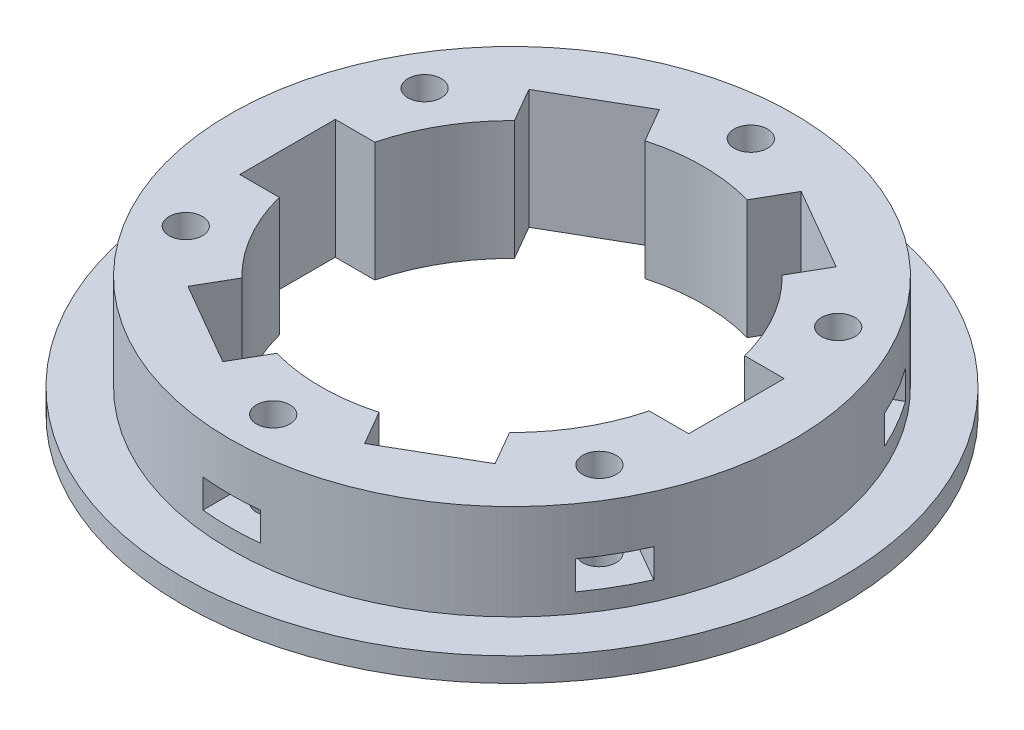
SolidWorks part; units mm, degrees
ref_plane "Front Plane" through (0, 0, 0) normal (0, 0, 1) x (1, 0, 0)
ref_plane "Top Plane" through (0, 0, 0) normal (0, 1, 0) x (1, 0, 0)
ref_plane "Right Plane" through (0, 0, 0) normal (1, 0, 0) x (0, 0, -1)
sketch "Sketch1" plane through (0, 0, 0) normal (0, 1, 0) x (1, 0, 0)
  circle A0 centre (0, 0) radius 34.5
  circle A1 centre (0, 0) radius 30 construction
  circle A2 centre (0, 0) radius 20
  dimension "D1" = 69
  dimension "D2" = 60
  dimension "D3" = 40
extrude "Boss-Extrude1" add sketch "Sketch1" along normal blind 2.5
sketch "Sketch2" plane through (0, 2.5, 0) normal (0, 1, 0) x (1, 0, 0)
  circle A0 centre (0, 0) radius 29.5
  circle A1 centre (0, 0) radius 20
  dimension "D1" = 59
  dimension "D2" = 40
extrude "Boss-Extrude2" add sketch "Sketch2" along normal blind 10
sketch "Sketch3" plane through (0, 12.5, 0) normal (0, 1, 0) x (1, 0, 0)
  line L0 (0, 0) -> (-34.5, 0) construction
  line L1 (0, 0) -> (0, -34.5) construction
  line L2 (-19.3649, 5) -> (-23.5, 5)
  line L3 (23.5, -5) -> (19.3649, -5) construction
  line L4 (23.5, -5) -> (23.5, 5) construction
  line L5 (23.5, 5) -> (19.3649, 5) construction
  line L6 (-23.5, -5) -> (-23.5, 5)
  line L7 (23.5, -5) -> (-23.5, 5) construction
  line L8 (23.5, 5) -> (-23.5, -5) construction
  line L9 (-19.3649, -5) -> (-23.5, -5)
  line L10 (-5.3523, 19.2705) -> (-7.4199, 22.8516)
  line L11 (-16.0801, 17.8516) -> (-7.4199, 22.8516)
  line L12 (-14.0126, 14.2705) -> (-16.0801, 17.8516)
  line L13 (14.0126, 14.2705) -> (16.0801, 17.8516)
  line L14 (7.4199, 22.8516) -> (16.0801, 17.8516)
  line L15 (5.3523, 19.2705) -> (7.4199, 22.8516)
  line L16 (19.3649, -5) -> (23.5, -5)
  line L17 (23.5, 5) -> (23.5, -5)
  line L18 (19.3649, 5) -> (23.5, 5)
  line L19 (5.3523, -19.2705) -> (7.4199, -22.8516)
  line L20 (16.0801, -17.8516) -> (7.4199, -22.8516)
  line L21 (14.0126, -14.2705) -> (16.0801, -17.8516)
  line L22 (-14.0126, -14.2705) -> (-16.0801, -17.8516)
  line L23 (-7.4199, -22.8516) -> (-16.0801, -17.8516)
  line L24 (-5.3523, -19.2705) -> (-7.4199, -22.8516)
  circle A0 centre (0, 0) radius 34.5 construction
  arc A1 (19.3649, -5) -> (19.3649, 5) centre (0, 0) ccw construction
  arc A2 (-19.3649, 5) -> (-19.3649, -5) centre (0, 0) ccw
  arc A3 (-5.3523, 19.2705) -> (-14.0126, 14.2705) centre (0, 0) ccw
  arc A4 (14.0126, 14.2705) -> (5.3523, 19.2705) centre (0, 0) ccw
  arc A5 (19.3649, -5) -> (19.3649, 5) centre (0, 0) ccw
  arc A6 (5.3523, -19.2705) -> (14.0126, -14.2705) centre (0, 0) ccw
  arc A7 (-14.0126, -14.2705) -> (-5.3523, -19.2705) centre (0, 0) ccw
  point P37 (0, 0)
  dimension "D1" = 47
  dimension "D3" = 40
  dimension "D2" = 10
  dimension "D4" = 6
sketch "Sketch4" plane through (0, 12.5, 0) normal (0, 1, 0) x (1, 0, 0)
  line L0 (0, 0) -> (-45.5771, 0) construction
  line L1 (0, 0) -> (-43.3013, -25) construction
  circle A0 centre (0, 0) radius 25 construction
  circle A1 centre (-21.6506, -12.5) radius 1.75
  circle A2 centre (-21.6506, 12.5) radius 1.75
  circle A3 centre (0, 25) radius 1.75
  circle A4 centre (21.6506, 12.5) radius 1.75
  circle A5 centre (21.6506, -12.5) radius 1.75
  circle A6 centre (0, -25) radius 1.75
  point P16 (0, 0)
  point P20 (0, 0)
  dimension "D1" = 50
  dimension "D2" = 30
  dimension "D3" = 3.5
  dimension "D4" = 6
extrude "Cut-Extrude2" cut sketch "Sketch4" against normal through all
extrude "Cut-Extrude1" cut sketch "Sketch3" against normal through all
ref_plane "Plane2" through (0, 7.5, 0) normal (0, 1, 0) x (1, 0, 0)
sketch "Sketch7" plane through (0, 7.5, 0) normal (0, 1, 0) x (1, 0, 0)
  line L0 (0, 0) -> (0, -34.5) construction
  line L1 (-18.6506, -10.7679) -> (-21.6506, -9.0359)
  line L2 (0, -21.5359) -> (-3, -23.2679)
  line L3 (-3, -23.2679) -> (-3, -29.3471)
  line L4 (-21.6506, -9.0359) -> (-26.9153, -12.0755)
  line L5 (-23.9153, -17.2716) -> (-18.6506, -14.2321)
  line L6 (3, -29.3471) -> (3, -23.2679)
  line L7 (3, -23.2679) -> (0, -21.5359)
  line L8 (0, -28.4641) -> (1.5, -27.5981) [skipped]
  line L9 (-3, -26.7321) -> (-1.5, -27.5981) [skipped]
  line L10 (-18.6506, -14.2321) -> (-18.6506, -10.7679)
  line L11 (-18.6506, 10.7679) -> (-18.6506, 14.2321)
  line L12 (-18.6506, 14.2321) -> (-23.9153, 17.2716)
  line L13 (-26.9153, 12.0755) -> (-21.6506, 9.0359)
  line L14 (-21.6506, 9.0359) -> (-18.6506, 10.7679)
  line L15 (0, 21.5359) -> (3, 23.2679)
  line L16 (3, 23.2679) -> (3, 29.3471)
  line L17 (-3, 29.3471) -> (-3, 23.2679)
  line L18 (-3, 23.2679) -> (0, 21.5359)
  line L19 (18.6506, 10.7679) -> (21.6506, 9.0359)
  line L20 (21.6506, 9.0359) -> (26.9153, 12.0755)
  line L21 (23.9153, 17.2716) -> (18.6506, 14.2321)
  line L22 (18.6506, 14.2321) -> (18.6506, 10.7679)
  line L23 (18.6506, -10.7679) -> (18.6506, -14.2321)
  line L24 (18.6506, -14.2321) -> (23.9153, -17.2716)
  line L25 (26.9153, -12.0755) -> (21.6506, -9.0359)
  line L26 (21.6506, -9.0359) -> (18.6506, -10.7679)
  circle A0 centre (0, 0) radius 34.5 construction
  circle A1 centre (0, -25) radius 3 construction
  arc A2 (-3, -29.3471) -> (3, -29.3471) centre (0, 0) ccw
  arc A3 (-26.9153, -12.0755) -> (-23.9153, -17.2716) centre (0, 0) ccw
  circle A4 centre (-21.6506, -12.5) radius 3 construction
  arc A5 (-23.9153, 17.2716) -> (-26.9153, 12.0755) centre (0, 0) ccw
  circle A6 centre (-21.6506, 12.5) radius 3 construction
  arc A7 (3, 29.3471) -> (-3, 29.3471) centre (0, 0) ccw
  circle A8 centre (0, 25) radius 3 construction
  arc A9 (26.9153, 12.0755) -> (23.9153, 17.2716) centre (0, 0) ccw
  circle A10 centre (21.6506, 12.5) radius 3 construction
  arc A11 (23.9153, -17.2716) -> (26.9153, -12.0755) centre (0, 0) ccw
  circle A12 centre (21.6506, -12.5) radius 3 construction
  point P54 (0, 0)
  dimension "D1" = 6
  dimension "D2" = 59
  dimension "D3" = 6
extrude "Cut-Extrude3" cut sketch "Sketch7" against normal blind 3
